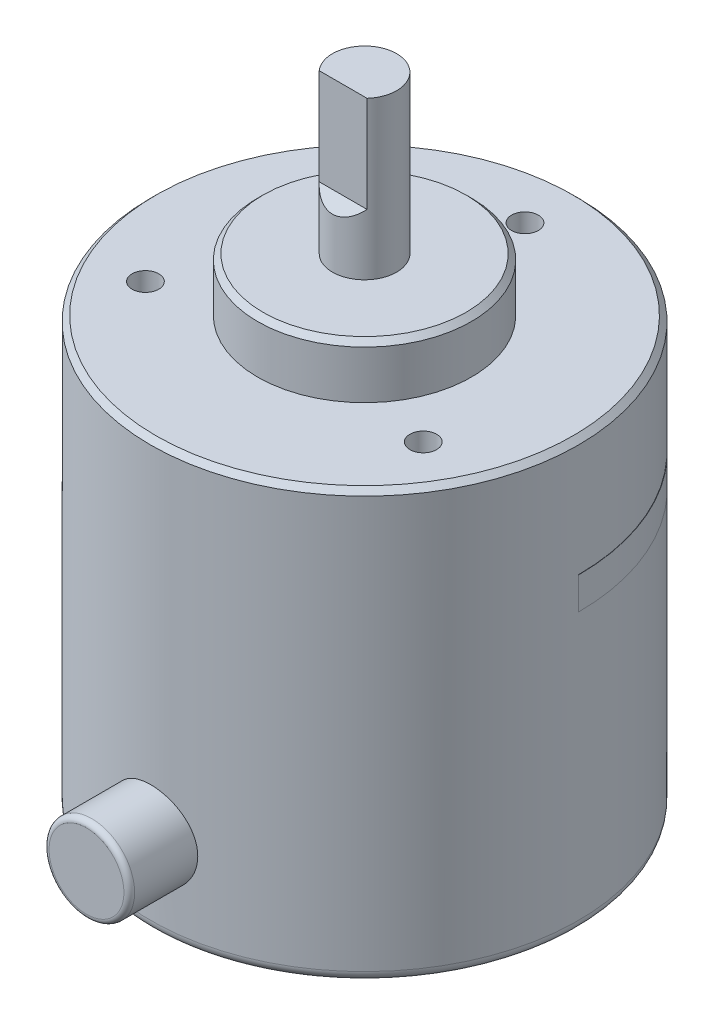
SolidWorks part; units mm, degrees
ref_plane "前视基准面" through (0, 0, 0) normal (0, 0, 1) x (1, 0, 0)
ref_plane "上视基准面" through (0, 0, 0) normal (0, 1, 0) x (1, 0, 0)
ref_plane "右视基准面" through (0, 0, 0) normal (1, 0, 0) x (0, 0, -1)
sketch "草图1" plane through (0, 0, 0) normal (0, 0, 1) x (1, 0, 0)
  line L0 (0, 0) -> (0, 59.7)
  line L1 (0, 59.7) -> (3, 59.7)
  line L2 (3, 59.7) -> (3, 45)
  line L3 (3, 45) -> (10, 45)
  line L4 (10, 45) -> (10, 40)
  line L5 (10, 40) -> (20, 40)
  line L6 (20, 40) -> (20, 0)
  line L7 (20, 0) -> (0, 0)
  dimension "D1" = 3
  dimension "D2" = 10
  dimension "D3" = 20
  dimension "D4" = 40
  dimension "D5" = 14.7
  dimension "D6" = 5
revolve "旋转1" add sketch "草图1" angle 360 about L0
sketch "草图2" plane through (0, 59.7, 0) normal (0, 1, 0) x (1, 0, 0)
  line L1 (6.4995, -7.0166) -> (-10.471, -7.0166)
  line L2 (6.4995, -7.0166) -> (6.4995, -2)
  line L3 (6.4995, -2) -> (-10.471, -2)
  line L4 (-10.471, -7.0166) -> (-10.471, -2)
  circle A0 centre (0, 0) radius 3 construction
  dimension "D1" = 2
extrude "切除-拉伸1" cut sketch "草图2" against normal blind 10
chamfer "倒角1" distance 1 angle 45 1 edges at (0, 49.7, 2)
sketch "草图3" plane through (0, 0, 0) normal (0, 0, 1) x (1, 0, 0)
  line L0 (-20, 0) -> (20, 0) construction
  circle A0 centre (0, 8) radius 4
  dimension "D1" = 8
  dimension "D2" = 8
extrude "凸台-拉伸1" add sketch "草图3" along normal blind 26
fillet "圆角1" radius 1 1 edges at (0, 0, -20)
fillet "圆角2" radius 0.5 1 edges at (4, 8, 26)
chamfer "倒角2" distance 0.5 angle 45 2 edges at (0, 40, -20) (0, 45, -10)
sketch "草图5" plane through (0, 40, 0) normal (0, 1, 0) x (1, 0, 0)
  line L1 (0, 15) -> (-12.9904, -7.5) construction
  line L2 (-12.9904, -7.5) -> (12.9904, -7.5) construction
  line L3 (12.9904, -7.5) -> (0, 15) construction
  circle A0 centre (0, 0) radius 15 construction
  dimension "D1" = 30
hole_wizard "M3 螺纹孔1" positions "草图6" profile "草图7" tap size "M3" standard "GB"
sketch "草图6" plane through (0, 40, 0) normal (0, 1, 0) x (1, 0, 0)
  point P0 (-12.9904, -7.5)
  point P3 (12.9904, -7.5)
  point P6 (0, 15)
sketch "草图7" plane through (-12.9904, 40, 7.5) normal (1, 0, 0) x (0, 0, 1)
  line L0 (0, 0) -> (0, 8.2511)
  line L1 (0, 8.2511) -> (1.25, 7.5)
  line L2 (1.25, 7.5) -> (1.25, 0)
  line L5 (1.25, 0) -> (0, 0)
  line L10 (0, 8.2511) -> (-1.25, 7.5) construction
  line L11 (0, -6.35) -> (0, 107.95) construction
  dimension "螺纹孔钻头直径" = 2.5
  dimension "螺纹孔钻头深度" = 7.5
  dimension "导头角度" = 118
cosmetic thread "孔螺蚊线1" parameters "D1"=6, "D2"=3
cosmetic thread "孔螺蚊线2" parameters "D1"=6, "D2"=3
cosmetic thread "孔螺蚊线3" parameters "D1"=6, "D2"=3
ref_plane "基准面1" through (0, 29, 0) normal (0, 1, 0) x (1, 0, 0)
sketch "草图8" plane through (0, 29, 0) normal (0, 1, 0) x (1, 0, 0)
  line L0 (20.025, 0) -> (-20.025, 0)
  arc A0 (20.025, 0) -> (-20.025, 0) centre (0, 0) ccw
  dimension "D1" = 40.05
extrude "凸台-拉伸2" add sketch "草图8" against normal blind 3
